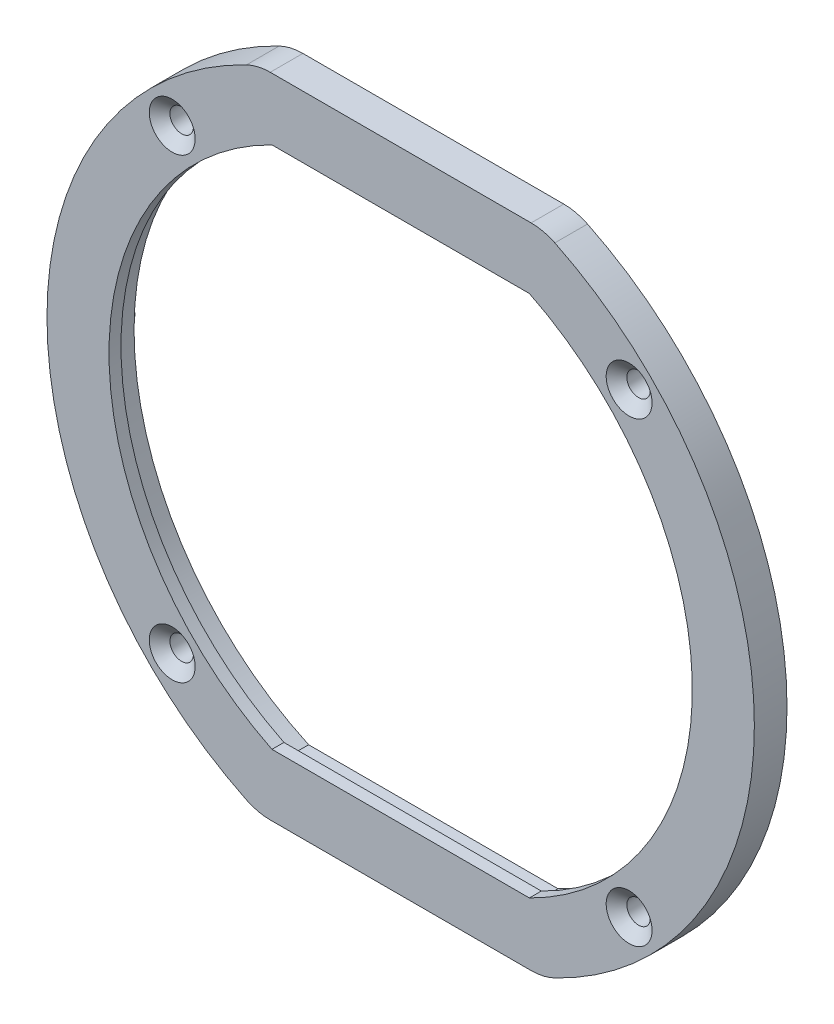
SolidWorks part; units mm, degrees
material "PVC 0.007 Plasticized"
ref_plane "Front Plane" through (0, 0, 0) normal (0, 0, 1) x (1, 0, 0)
ref_plane "Top Plane" through (0, 0, 0) normal (0, 1, 0) x (1, 0, 0)
ref_plane "Right Plane" through (0, 0, 0) normal (1, 0, 0) x (0, 0, -1)
sketch "Sketch1" plane through (0, 0, 0) normal (0, 0, 1) x (1, 0, 0)
  line L0 (0, -48.1) -> (0, 48.1) construction
  line L1 (-23.6506, 48.1) -> (23.6506, 48.1)
  line L2 (-23.6506, -48.1) -> (23.6506, -48.1)
  line L3 (0, -59.5) -> (0, 59.5) construction
  line L4 (-26.1677, 59.5) -> (26.1677, 59.5)
  line L5 (-26.1677, -59.5) -> (26.1677, -59.5)
  arc A0 (-26.1677, 59.5) -> (-26.1677, -59.5) centre (0, 0) ccw
  arc A1 (-23.6506, 48.1) -> (-23.6506, -48.1) centre (0, 0) ccw
  arc A2 (23.6506, -48.1) -> (23.6506, 48.1) centre (0, 0) ccw
  arc A3 (26.1677, -59.5) -> (26.1677, 59.5) centre (0, 0) ccw
  point P6 (0, 0)
  point P9 (0, 48.1)
  point P13 (0, -48.1)
  point P15 (0, 0)
  point P17 (0, 59.5)
  point P20 (0, -59.5)
  dimension "D1" = 130
  dimension "D2" = 107.2
  dimension "D3" = 96.2
  dimension "D4" = 119
extrude "Boss-Extrude1" add sketch "Sketch1" along normal blind 6
hole_wizard "CSK for #8 Flat Head Machine Screw (100)1" positions "Sketch2" profile "Sketch4" countersink size "#8" standard "ANSI Inch" end condition through all
sketch "Sketch2" plane through (0, 0, 6) normal (0, 0, 1) x (1, 0, 0)
  line L1 (-41.985, -41.985) -> (41.985, -41.985) construction
  line L2 (-41.985, -41.985) -> (-41.985, 41.985) construction
  line L3 (-41.985, 41.985) -> (41.985, 41.985) construction
  line L4 (41.985, -41.985) -> (41.985, 41.985) construction
  line L5 (-41.985, -41.985) -> (41.985, 41.985) construction
  line L6 (-41.985, 41.985) -> (41.985, -41.985) construction
  point P1 (0, 0)
  point P2 (41.985, 41.985)
  point P39 (-41.985, -41.985)
  point P40 (-41.985, 41.985)
  point P41 (41.985, -41.985)
  dimension "D1" = 83.97
sketch "Sketch4" plane through (0, 0, 6) normal (1, 0, 0) x (0, -1, 0)
  line L0 (0, 0) -> (0, 6)
  line L1 (0, 6) -> (2.1526, 6)
  line L2 (2.1526, 6) -> (2.1526, 1.7317)
  line L3 (2.1526, 1.7317) -> (4.2164, 0)
  line L5 (4.2164, 0) -> (0, 0)
  line L6 (-2.1526, 1.7317) -> (-4.2164, 0) construction
  line L11 (0, -6.35) -> (0, 107.95) construction
  dimension "Thru Hole Dia." = 4.3053
  dimension "Thru Hole Depth" = 6
  dimension "Near C'Sink Dia." = 8.4328
  dimension "Near C'Sink Angle" = 100
sketch "Sketch5" plane through (0, 0, 0) normal (0, 0, -1) x (-1, 0, 0)
  line L0 (59.2455, 0) -> (-59.2455, 0) construction
  circle A0 centre (-59.2455, 0) radius 1.905
  circle A1 centre (59.2455, 0) radius 1.905
  point P4 (0, 0)
  dimension "D2" = 3.81
  dimension "D1" = 118.491
extrude "Boss-Extrude2" add sketch "Sketch5" along normal blind 2.5
fillet "Fillet1" radius 10 4 edges at (26.1677, -59.5, 3) (-26.1677, -59.5, 3) (26.1677, 59.5, 3) (-26.1677, 59.5, 3)
sketch "Sketch6" plane through (0, 0, 0) normal (0, 0, -1) x (-1, 0, 0)
  line L0 (22.9129, 50) -> (-22.9129, 50)
  line L1 (-22.9129, -50) -> (22.9129, -50)
  arc A0 (22.9129, -50) -> (22.9129, 50) centre (0, 0) ccw
  arc A5 (-22.9129, 50) -> (-22.9129, -50) centre (0, 0) ccw
  dimension "D2" = 110
  dimension "D1" = 100
extrude "Cut-Extrude1" cut sketch "Sketch6" against normal blind 3.8
